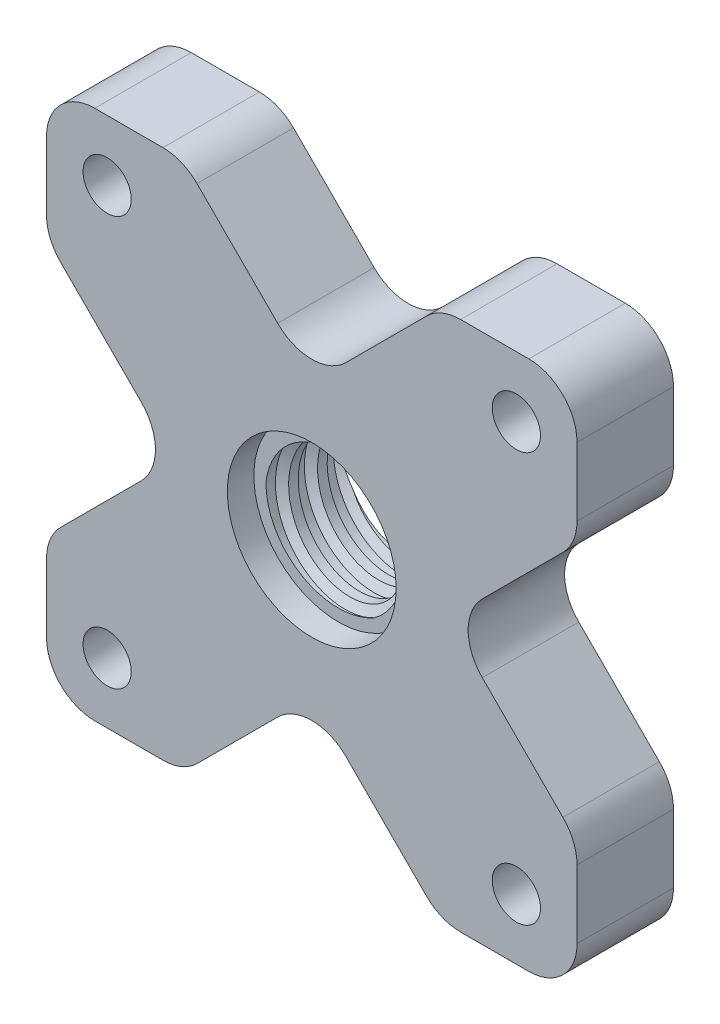
SolidWorks part; units mm, degrees
ref_plane "Front Plane" through (0, 0, 0) normal (0, 0, 1) x (1, 0, 0)
ref_plane "Top Plane" through (0, 0, 0) normal (0, 1, 0) x (1, 0, 0)
ref_plane "Right Plane" through (0, 0, 0) normal (1, 0, 0) x (0, 0, -1)
sketch "Sketch2" plane through (0, 0, 0) normal (0, 0, 1) x (1, 0, 0)
  line L0 (15.4289, 27.5) -> (22.5, 27.5)
  line L1 (-22.5, -27.5) -> (-15.4289, -27.5)
  line L2 (-27.5, -22.5) -> (-27.5, -15.4289)
  line L3 (-22.5, 27.5) -> (-15.4289, 27.5)
  line L4 (27.5, -22.5) -> (27.5, -15.4289)
  line L5 (-27.5, -27.5) -> (27.5, 27.5) construction
  line L6 (-27.5, 27.5) -> (27.5, -27.5) construction
  line L7 (-27.5, 15.4289) -> (-27.5, 22.5)
  line L8 (-11.8934, -26.0355) -> (-3.5355, -17.6777)
  line L9 (-26.0355, -11.8934) -> (-17.6777, -3.5355)
  line L10 (-26.0355, 11.8934) -> (-17.6777, 3.5355)
  line L11 (-11.8934, 26.0355) -> (-3.5355, 17.6777)
  line L12 (3.5355, 17.6777) -> (11.8934, 26.0355)
  line L13 (15.4289, -27.5) -> (22.5, -27.5)
  line L14 (27.5, 15.4289) -> (27.5, 22.5)
  line L15 (17.6777, 3.5355) -> (26.0355, 11.8934)
  line L16 (17.6777, -3.5355) -> (26.0355, -11.8934)
  line L17 (3.5355, -17.6777) -> (11.8934, -26.0355)
  arc A0 (-27.5, -15.4289) -> (-26.0355, -11.8934) centre (-22.5, -15.4289) cw
  arc A1 (-15.4289, -27.5) -> (-11.8934, -26.0355) centre (-15.4289, -22.5) ccw
  arc A2 (15.4289, -27.5) -> (11.8934, -26.0355) centre (15.4289, -22.5) cw
  arc A3 (26.0355, -11.8934) -> (27.5, -15.4289) centre (22.5, -15.4289) cw
  arc A4 (27.5, 15.4289) -> (26.0355, 11.8934) centre (22.5, 15.4289) cw
  arc A5 (11.8934, 26.0355) -> (15.4289, 27.5) centre (15.4289, 22.5) cw
  arc A6 (-27.5, 15.4289) -> (-26.0355, 11.8934) centre (-22.5, 15.4289) ccw
  arc A7 (-11.8934, 26.0355) -> (-15.4289, 27.5) centre (-15.4289, 22.5) ccw
  arc A8 (-17.6777, -3.5355) -> (-17.6777, 3.5355) centre (-21.2132, 0) ccw
  arc A9 (17.6777, 3.5355) -> (17.6777, -3.5355) centre (21.2132, 0) ccw
  arc A10 (-3.5355, -17.6777) -> (3.5355, -17.6777) centre (0, -21.2132) cw
  arc A11 (3.5355, 17.6777) -> (-3.5355, 17.6777) centre (0, 21.2132) cw
  arc A12 (-22.5, -27.5) -> (-27.5, -22.5) centre (-22.5, -22.5) cw
  arc A13 (22.5, -27.5) -> (27.5, -22.5) centre (22.5, -22.5) ccw
  arc A14 (22.5, 27.5) -> (27.5, 22.5) centre (22.5, 22.5) cw
  arc A15 (-27.5, 22.5) -> (-22.5, 27.5) centre (-22.5, 22.5) cw
  circle A16 centre (-21.2132, 21.2132) radius 2.5
  circle A20 centre (0, 0) radius 6.634
  circle A21 centre (21.2132, 21.2132) radius 2.5
  circle A22 centre (21.2132, -21.2132) radius 2.5
  circle A23 centre (-21.2132, -21.2132) radius 2.5
  point P0 (0, 0)
  point P67 (0, 0)
  dimension "D7" = 5
  dimension "D8" = 5
  dimension "D10" = 13.268
  dimension "D1" = 55
  dimension "D2" = 10
  dimension "D3" = 10
  dimension "D4" = 10
  dimension "D5" = 10
  dimension "D6" = 55
  dimension "D9" = 30
  dimension "D11" = 4
extrude "Boss-Extrude1" add sketch "Sketch2" along normal blind 10
sketch "Sketch3" plane through (0, 0, 0) normal (0, 0, -1) x (-1, 0, 0)
  circle A0 centre (0, 0) radius 6.634 construction
  circle A1 centre (0, 0) radius 6.634
curve "Helix/Spiral1" pitch 3 height 8.25 radius 6.634 centre (0, 0, 0) axis (0, 0, 1) start towards (0, 1, 0)
sketch "Sketch4" plane through (0, 0, 0) normal (1, 0, 0) x (0, 0, -1)
  line L0 (-0.5, 7.5) -> (0.5, 7.5)
  line L2 (0.5, 7.5) -> (1, 6.634)
  line L3 (1, 6.634) -> (-1, 6.634)
  line L4 (-1, 6.634) -> (-0.5, 7.5)
  point P2 (0, 7.5)
  point P3 (0, 6.634)
  dimension "D1" = 1
  dimension "D2" = 1
  dimension "D3" = 120
sweep "Cut-Sweep4" cut profiles "Sketch4" path "Helix/Spiral1" align with end faces yes
sketch "Sketch6" plane through (0, 0, 10) normal (0, 0, 1) x (1, 0, 0)
  circle A0 centre (0, 0) radius 8.75
  dimension "D1" = 17.5
extrude "Cut-Extrude2" cut sketch "Sketch6" against normal blind 2.75
